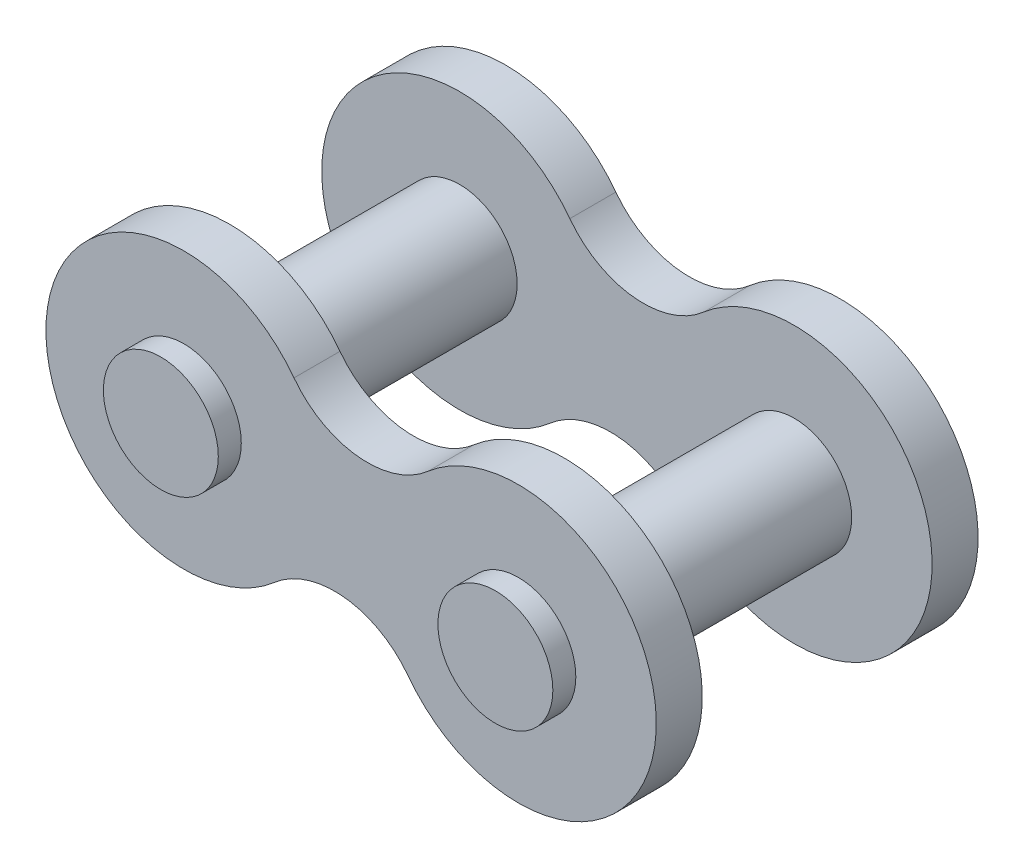
SolidWorks part; units mm, degrees
material "7050-T73510"
ref_plane "Ön Düzlem" through (0, 0, 0) normal (0, 0, 1) x (1, 0, 0)
ref_plane "Üst Düzlem" through (0, 0, 0) normal (0, 1, 0) x (1, 0, 0)
ref_plane "Sağ Düzlem" through (0, 0, 0) normal (1, 0, 0) x (0, 0, -1)
sketch "Çizim1" plane through (0, 0, 0) normal (0, 0, 1) x (1, 0, 0)
  line L0 (0, -73.7578) -> (-232.1205, -73.7578) construction
  line L1 (-24.0045, 69.7424) -> (-243.7247, -5.8828) construction
  line L2 (0, 70) -> (0, 0) construction
  line L3 (-232.1205, -73.7578) -> (0, -73.7578) construction
  line L4 (-243.7247, -5.8828) -> (-24.0045, 69.7424) construction
  line L5 (0, 70) -> (14.5538, 68.4703) construction
  arc A0 (0, -73.7578) -> (-24.0045, 69.7424) centre (0, 0) ccw construction
  arc A1 (-243.7247, -5.8828) -> (-232.1205, -73.7578) centre (-232.3705, -38.8711) ccw construction
  circle A5 centre (0, 70) radius 2.5
  circle A7 centre (14.5538, 68.4703) radius 2.5
  arc A8 (9.7602, 64.8619) -> (10.6152, 72.9966) centre (14.5538, 68.4703) ccw
  arc A9 (10.6152, 72.9966) -> (4.7936, 73.6085) centre (7.9894, 76.0141) cw
  arc A10 (4.7936, 73.6085) -> (3.9386, 65.4737) centre (0, 70) ccw
  arc A11 (9.7602, 64.8619) -> (3.9386, 65.4737) centre (6.5644, 62.4562) ccw
  dimension "D2" = 5
extrude "Yükseklik-Ekstrüzyon1" add sketch "Çizim1" along normal blind 2
extrude "Yükseklik-Ekstrüzyon2" add sketch "Çizim1<2>" against normal blind 2 from offset 10 separate body offset against normal yes
sketch "Çizim1<2>" plane through (0, 0, 0) normal (0, 0, 1) x (1, 0, 0) same geometry as "Çizim1"
extrude "Yükseklik-Ekstrüzyon3" add sketch "Çizim1<6>" along normal mid plane 16 from offset 5 separate body contours A5 | A7 region at (0, 70, 0) region at (14.5538, 68.4703, 0) offset against normal yes
sketch "Çizim1<6>" plane through (0, 0, 0) normal (0, 0, 1) x (1, 0, 0) same geometry as "Çizim1"
ref_plane "ortaakisdüzlem" through (0, 0, -5) normal (0, 0, 1) x (1, 0, 0)
